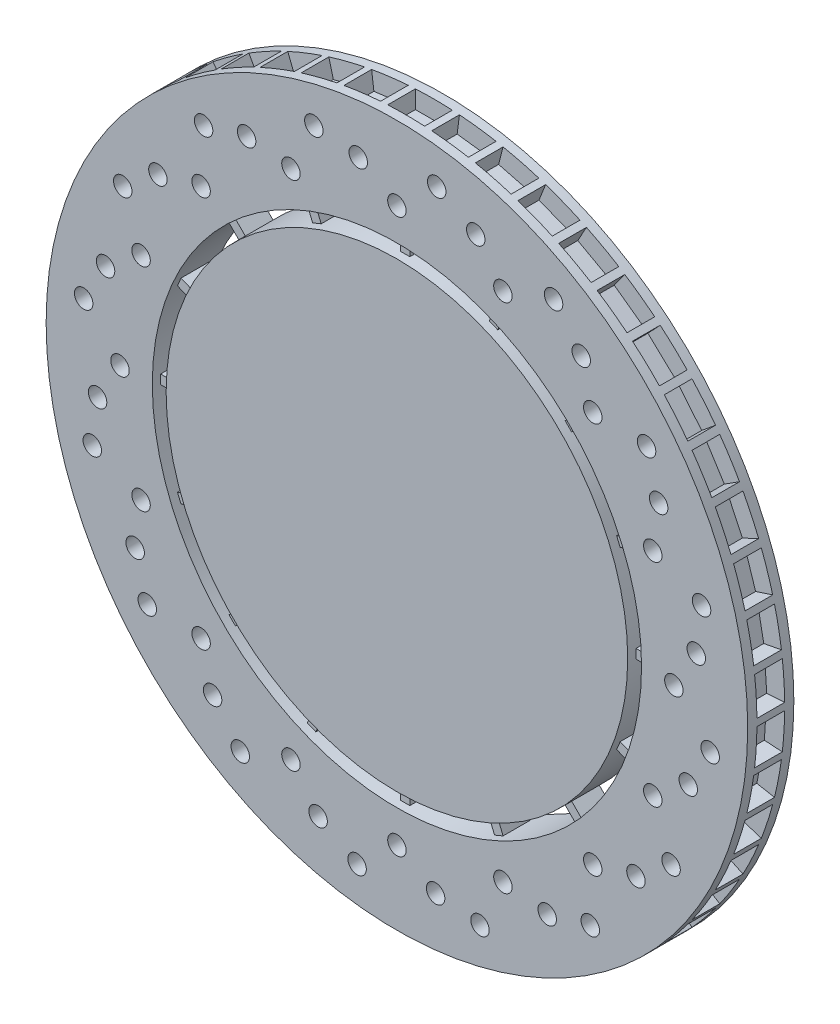
SolidWorks part; units mm, degrees
ref_plane "Front Plane" through (0, 0, 0) normal (0, 0, 1) x (1, 0, 0)
ref_plane "Top Plane" through (0, 0, 0) normal (0, 1, 0) x (1, 0, 0)
ref_plane "Right Plane" through (0, 0, 0) normal (1, 0, 0) x (0, 0, -1)
sketch "Sketch1" plane through (0, 0, 0) normal (0, 0, 1) x (1, 0, 0)
  circle A0 centre (0, 0) radius 125
  dimension "D1" = 250
extrude "Boss-Extrude1" add sketch "Sketch1" along normal blind 35
chamfer "Chamfer1" distance 40 angle 15 1 edges at (125, 0, 0) first distance on face at (125, 0, 0)
sketch "Sketch2" plane through (0, 0, 35) normal (0, 0, 1) x (1, 0, 0)
  circle A0 centre (0, 0) radius 132.5
  circle A1 centre (0, 0) radius 190
  dimension "D1" = 265
  dimension "D2" = 380
extrude "Boss-Extrude2" add sketch "Sketch2" against normal blind 25 separate body
sketch "Sketch3" plane through (0, 0, 0) normal (1, 0, 0) x (0, 0, -1)
  line L0 (-35, 190) -> (-10, 190) construction
  line L5 (-22.5, 220) -> (-22.5, 190) construction
  dimension "D1" = 30
ref_plane "Plane1" through (0, 0, 22.5) normal (0, 0, 1) x (1, 0, 0)
ref_axis "Axis1" through (0, 0, 10) along (0, 0, 1)
sketch "Sketch4" plane through (0, 0, 0) normal (0, 1, 0) x (1, 0, 0)
  line L0 (-190, -35) -> (190, -35) construction
  line L1 (-2.5, -30.5) -> (2.5, -30.5)
  line L2 (-2.5, -30.5) -> (-2.5, -15.5)
  line L3 (-2.5, -15.5) -> (2.5, -15.5)
  line L4 (2.5, -30.5) -> (2.5, -15.5)
  line L5 (-2.5, -30.5) -> (2.5, -15.5) construction
  line L6 (-2.5, -15.5) -> (2.5, -30.5) construction
  point P2 (0, -23)
  dimension "D1" = 12
  dimension "D2" = 15
  dimension "D3" = 5
extrude "Boss-Extrude3" add sketch "Sketch4" along normal up to surface (132.4764 mm away) up to face at (132.5, 0, 10)
pattern_circular "CirPattern1" count 16 over 360 about axis through (0, 0, 10) along (0, 0, 1) of "Boss-Extrude3"
sketch "Sketch6" plane through (0, 0, 10) normal (0, 0, -1) x (-1, 0, 0)
  circle A0 centre (0, 150) radius 5
  circle A1 centre (20.9548, 162.1357) radius 5
  circle A2 centre (45, 165) radius 5
  arc A3 (0, 150) -> (45, 165) centre (39.9284, 105.2147) cw construction
  dimension "D4" = 45
  dimension "D5" = 60
  dimension "D1" = 150
  dimension "D2" = 10
  dimension "D3" = 165
extrude "Cut-Extrude2" cut sketch "Sketch6" against normal through all
pattern_circular "CirPattern3" count 16 over 360 about axis through (0, 0, 10) along (0, 0, 1) of "Cut-Extrude2"
sketch "Sketch7" plane through (0, 0, 0) normal (0, 1, 0) x (1, 0, 0)
  line L0 (0, -10) -> (0, -35) construction
  line L1 (-10, -15) -> (10, -15)
  line L2 (-10, -15) -> (-10, -30)
  line L3 (-10, -30) -> (10, -30)
  line L4 (10, -15) -> (10, -30)
  line L5 (-10, -15) -> (10, -30) construction
  line L6 (-10, -30) -> (10, -15) construction
  line L7 (190, -10) -> (-190, -10) construction
  line L8 (-190, -35) -> (190, -35) construction
  point P0 (0, -22.5)
  dimension "D1" = 15
  dimension "D2" = 20
extrude "Cut-Extrude3" cut sketch "Sketch7" along normal through all from offset 180
pattern_circular "CirPattern4" count 50 over 360 about axis through (0, 0, 10) along (0, 0, 1) of "Cut-Extrude3"
